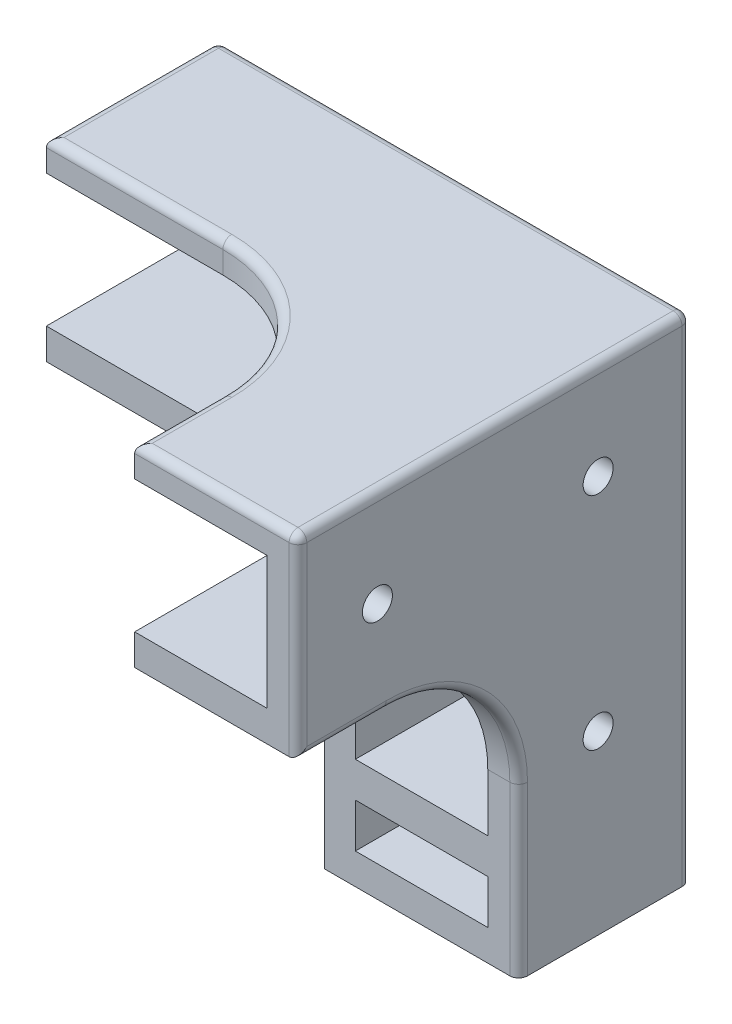
SolidWorks part; units mm, degrees
ref_plane "Front Plane" through (0, 0, 0) normal (0, 0, 1) x (1, 0, 0)
ref_plane "Top Plane" through (0, 0, 0) normal (0, 1, 0) x (1, 0, 0)
ref_plane "Right Plane" through (0, 0, 0) normal (1, 0, 0) x (0, 0, -1)
sketch "Sketch1" plane through (0, 0, 0) normal (0, 0, 1) x (1, 0, 0)
  line L1 (-5.6994, 32.9163) -> (16.3006, 32.9163)
  line L2 (-5.6994, 10.9163) -> (-5.6994, -23.0837)
  line L3 (-5.6994, -23.0837) -> (16.3006, -23.0837)
  line L4 (16.3006, 32.9163) -> (16.3006, -23.0837)
  line L5 (-5.6994, 10.9163) -> (-37.1994, 10.9163)
  line L7 (-5.6994, 32.9163) -> (-37.1994, 32.9163)
  line L8 (-37.1994, 10.9163) -> (-37.1994, 32.9163)
  dimension "D1" = 22
  dimension "D2" = 22
  dimension "D3" = 56
  dimension "D4" = 53.5
extrude "Boss-Extrude1" add sketch "Sketch1" along normal blind 19.5
sketch "Sketch3" plane through (0, 0, 19.5) normal (0, 0, 1) x (1, 0, 0)
  line L1 (16.3006, 32.9163) -> (-2.1994, 32.9163)
  line L2 (16.3006, 32.9163) -> (16.3006, 10.9163)
  line L3 (16.3006, 10.9163) -> (-2.1994, 10.9163)
  line L4 (-2.1994, 32.9163) -> (-2.1994, 10.9163)
  dimension "D1" = 18.5
  dimension "D2" = 22
extrude "Boss-Extrude2" add sketch "Sketch3" along normal blind 25
sketch "Sketch5" plane through (0, 0, 44.5) normal (0, 0, 1) x (1, 0, 0)
  line L0 (-37.1994, 32.9163) -> (-37.1994, 10.9163) construction
  line L1 (-37.1994, 29.4163) -> (12.8006, 29.4163)
  line L2 (-37.1994, 29.4163) -> (-37.1994, 14.4163)
  line L3 (-37.1994, 14.4163) -> (12.8006, 14.4163)
  line L4 (12.8006, 29.4163) -> (12.8006, 14.4163)
  line L5 (16.3006, 10.9163) -> (16.3006, 32.9163) construction
  line L6 (-2.1994, 4.4163) -> (12.8006, 4.4163)
  line L7 (-2.1994, 4.4163) -> (-2.1994, -10.5837)
  line L8 (-2.1994, -10.5837) -> (12.8006, -10.5837)
  line L9 (12.8006, 4.4163) -> (12.8006, -10.5837)
  line L12 (-2.1994, 32.9163) -> (-37.1994, 32.9163) construction
  line L13 (-2.1994, 10.9163) -> (16.3006, 10.9163) construction
  line L15 (16.3006, -23.0837) -> (16.3006, 10.9163) construction
  line L16 (-5.6994, -23.0837) -> (16.3006, -23.0837) construction
  line L17 (-2.1994, -14.5837) -> (12.8006, -14.5837)
  line L18 (-2.1994, -14.5837) -> (-2.1994, -19.5837)
  line L19 (-2.1994, -19.5837) -> (12.8006, -19.5837)
  line L20 (12.8006, -14.5837) -> (12.8006, -19.5837)
  dimension "D1" = 3.5
  dimension "D2" = 6.5
  dimension "D3" = 15
  dimension "D4" = 3.5
  dimension "D5" = 15
  dimension "D6" = 15
  dimension "D7" = 3.5
  dimension "D8" = 15
  dimension "D9" = 4
  dimension "D10" = 3.5
extrude "Cut-Extrude1" cut sketch "Sketch5" against normal offset from surface (40.5 mm away) 4 up to face at (-8.8661, 6.9163, 0)
sketch "Sketch7" plane through (16.3006, 0, 0) normal (1, 0, 0) x (0, 0, -1)
  line L0 (-34.5, 10.9163) -> (-19.5, 10.9163)
  line L1 (-44.5, 10.9163) -> (-19.5, 10.9163) construction
  line L2 (-19.5, 10.9163) -> (-19.5, -4.0837)
  line L3 (-19.5, -23.0837) -> (-19.5, 10.9163) construction
  arc A0 (-34.5, 10.9163) -> (-19.5, -4.0837) centre (-34.5, -4.0837) cw
  dimension "D1" = 15
extrude "Boss-Extrude4" add sketch "Sketch7" against normal blind 3.5
sketch "Sketch8" plane through (0, 0, 0) normal (0, 0, -1) x (-1, 0, 0)
  line L0 (5.6994, 10.9163) -> (20.6994, 10.9163)
  line L1 (37.1994, 10.9163) -> (5.6994, 10.9163) construction
  line L2 (5.6994, 10.9163) -> (5.6994, -4.0837)
  line L3 (5.6994, 10.9163) -> (5.6994, -23.0837) construction
  arc A0 (20.6994, 10.9163) -> (5.6994, -4.0837) centre (20.6994, -4.0837) ccw
  dimension "D1" = 15
extrude "Boss-Extrude5" add sketch "Sketch8" against normal blind 3.5
sketch "Sketch9" plane through (0, 32.9163, 0) normal (0, 1, 0) x (1, 0, 0)
  line L0 (-2.1994, -34.5) -> (-2.1994, -19.5)
  line L1 (-2.1994, -44.5) -> (-2.1994, -19.5) construction
  line L2 (-2.1994, -19.5) -> (-17.1994, -19.5)
  line L3 (-2.1994, -19.5) -> (-37.1994, -19.5) construction
  arc A0 (-2.1994, -34.5) -> (-17.1994, -19.5) centre (-17.1994, -34.5) ccw
  dimension "D1" = 15
extrude "Boss-Extrude6" add sketch "Sketch9" against normal blind 3.5
fillet "Fillet3" radius 3 1 edges
sketch "Sketch11" plane through (0, 0, 0) normal (0, 0, -1) x (-1, 0, 0)
  line L0 (-0.3006, -23.0837) -> (-0.3006, 16.9163) construction
  line L2 (5.6994, -23.0837) -> (-16.3006, -23.0837) construction
  line L5 (5.6994, -4.0837) -> (5.6994, -23.0837) construction
  text T0 "ALFR3D" font "Murder Of Mayday" height 10
  dimension "D1" = 6
  dimension "D2" = 40
extrude "Cut-Extrude3" [suppressed] cut sketch "Sketch11" against normal blind 1
sketch "Sketch12" plane through (0, 0, 0) normal (0, 0, -1) x (-1, 0, 0)
  line L0 (37.1994, 21.9163) -> (-16.3006, 21.9163) construction
  line L1 (37.1994, 32.9163) -> (37.1994, 10.9163) construction
  line L2 (-16.3006, -23.0837) -> (-16.3006, 32.9163) construction
  line L3 (-12.8006, 14.4163) -> (-12.8006, 29.4163) construction
  circle A0 centre (-5.3006, 21.9163) radius 1.7
  circle A1 centre (10.9494, 21.9163) radius 1.7
  circle A2 centre (27.1994, 21.9163) radius 1.7
  dimension "D4" = 3.4
  dimension "D1" = 7.5
  dimension "D2" = 10
  dimension "D3" = 16.25
extrude "Cut-Extrude4" cut sketch "Sketch12" against normal blind 5
sketch "Sketch13" plane through (-5.6994, 0, 0) normal (-1, 0, 0) x (0, 0, 1)
  line L0 (4, 4.4163) -> (19.5, 4.4163) construction
  line L1 (19.5, 10.9163) -> (19.5, -23.0837) construction
  circle A0 centre (10.5, -3.0837) radius 1.7
  dimension "D2" = 9
  dimension "D3" = 3.4
  dimension "D1" = 7.5
extrude "Cut-Extrude5" cut sketch "Sketch13" against normal blind 45
sketch "Sketch14" plane through (16.3006, 0, 0) normal (1, 0, 0) x (0, 0, -1)
  line L0 (-10.5, -3.0837) -> (-10.5, 32.9163) construction
  line L1 (-44.5, 32.9163) -> (0, 32.9163) construction
  line L2 (-44.5, 21.9163) -> (-10.5, 21.9163) construction
  line L3 (-44.5, 10.9163) -> (-44.5, 32.9163) construction
  circle A0 centre (-10.5, 21.9163) radius 1.7
  circle A1 centre (-35.5, 21.9163) radius 1.7
  dimension "D1" = 3.4
  dimension "D2" = 9
extrude "Cut-Extrude6" cut sketch "Sketch14" against normal blind 45
sketch "Sketch15" plane through (0, -23.0837, 0) normal (0, -1, 0) x (1, 0, 0)
  line L0 (16.3006, 9.75) -> (-5.6994, 9.75) construction
  line L1 (16.3006, 19.5) -> (16.3006, 0) construction
  line L2 (-5.6994, 19.5) -> (-5.6994, 0) construction
  line L3 (5.3006, 19.5) -> (5.3006, 0) construction
  line L4 (-5.6994, 19.5) -> (16.3006, 19.5) construction
  line L5 (-5.6994, 0) -> (16.3006, 0) construction
  circle A0 centre (5.3006, 9.75) radius 1.7
  dimension "D1" = 3.4
extrude "Cut-Extrude7" cut sketch "Sketch15" against normal blind 4
fillet "Fillet4" radius 1 16 edges at (-28.9494, 10.9163, 0) (-10.0928, 6.5229, 0) (16.3006, 6.5229, 23.8934) (-6.5928, 32.9163, 23.8934) (-37.1994, 21.9163, 0) (-5.6994, -13.5837, 0) (-37.1994, 32.9163, 9.75) (-10.4494, 32.9163, 0) (7.0506, 32.9163, 44.5) (16.3006, 21.9163, 44.5) (16.3006, 32.9163, 22.25) (16.3006, 4.9163, 0)
